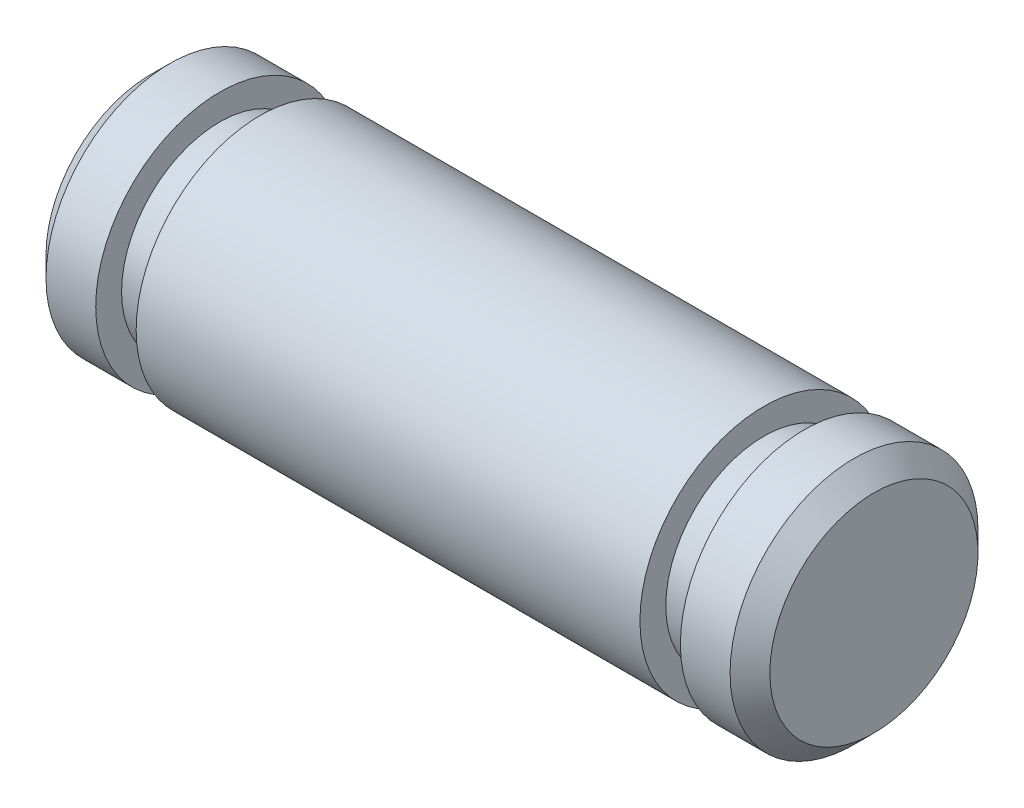
SolidWorks part; units mm, degrees
material "AISI 304"
ref_plane "Front Plane" through (0, 0, 0) normal (0, 0, 1) x (1, 0, 0)
ref_plane "Top Plane" through (0, 0, 0) normal (0, 1, 0) x (1, 0, 0)
ref_plane "Right Plane" through (0, 0, 0) normal (1, 0, 0) x (0, 0, -1)
sketch "Sketch1" plane through (0, 0, 0) normal (0, 0, 1) x (1, 0, 0)
  line L0 (-6.9342, 0) -> (-6.9342, 1.9939)
  line L1 (-6.9342, 1.9939) -> (-6.5532, 2.3749)
  line L2 (-6.5532, 2.3749) -> (-5.6007, 2.3749)
  line L3 (-5.6007, 2.3749) -> (-5.6007, 1.8796)
  line L4 (-5.6007, 1.8796) -> (-4.826, 1.8796)
  line L5 (-4.826, 1.8796) -> (-4.826, 2.3749)
  line L6 (-4.826, 2.3749) -> (4.826, 2.3749)
  line L7 (4.826, 2.3749) -> (4.826, 1.8796)
  line L8 (4.826, 1.8796) -> (5.6007, 1.8796)
  line L9 (5.6007, 1.8796) -> (5.6007, 2.3749)
  line L10 (5.6007, 2.3749) -> (6.5532, 2.3749)
  line L11 (6.5532, 2.3749) -> (6.9342, 1.9939)
  line L12 (6.9342, 1.9939) -> (6.9342, 0)
  line L13 (6.9342, 0) -> (-6.9342, 0)
  line L14 (6.9342, 0) -> (-6.9342, 0) construction
revolve "Revolve1" add sketch "Sketch1" angle 360 about L14 reverse direction yes
ref_plane "Plane1" through (5.2134, 0, 0) normal (1, 0, 0) x (0, 0, -1)
ref_plane "Plane2" through (-5.2134, 0, 0) normal (1, 0, 0) x (0, 0, -1)
ref_plane "p1 XY" through (0, 0, 0) normal (1, 0, 0) x (0, 0, -1)
ref_plane "p1 XZ" through (0, 0, 0) normal (0, -1, 0) x (-1, 0, 0)
ref_plane "p1 YZ" through (0, 0, 2.3749) normal (0, 0, -1) x (-1, 0, 0)
ref_axis "p1 X" through (0, 0, 80.9) along (0, 0, -1)
ref_axis "p1 Y" through (0, -50, 2.3749) along (0, 1, 0)
ref_axis "p1 Z" through (80.9, 0, 2.3749) along (-1, 0, 0)
sketch3d "p1"
  point P0 (0, 0, 2.3749)
ref_plane "p2 XY" through (0, 0, 0) normal (1, 0, 0) x (0, 0, -1)
ref_plane "p2 XZ" through (0, 0, 0) normal (0, -1, 0) x (-1, 0, 0)
ref_plane "p2 YZ" through (0, 0, -2.3749) normal (0, 0, -1) x (-1, 0, 0)
ref_axis "p2 X" through (0, 0, 80.9) along (0, 0, -1)
ref_axis "p2 Y" through (0, -50, -2.3749) along (0, 1, 0)
ref_axis "p2 Z" through (80.9, 0, -2.3749) along (-1, 0, 0)
sketch3d "p2"
  point P0 (0, 0, -2.3749)
ref_plane "pin XY" through (0, 0, 0) normal (1, 0, 0) x (0, 0, -1)
ref_plane "pin XZ" through (0, 0, 0) normal (0, -1, 0) x (-1, 0, 0)
ref_plane "pin YZ" through (0, 0, 0) normal (0, 0, -1) x (-1, 0, 0)
ref_axis "pin X" through (0, 0, 80.9) along (0, 0, -1)
ref_axis "pin Y" through (0, -50, 0) along (0, 1, 0)
ref_axis "pin Z" through (80.9, 0, 0) along (-1, 0, 0)
sketch3d "pin"
  point P0 (0, 0, 0)
ref_plane "rr1 XY" through (5.2134, 0, 0) normal (1, 0, 0) x (0, 0, -1)
ref_plane "rr1 XZ" through (0, 0, 0) normal (0, -1, 0) x (-1, 0, 0)
ref_plane "rr1 YZ" through (0, 0, 0) normal (0, 0, -1) x (-1, 0, 0)
ref_axis "rr1 X" through (5.2134, 0, 80.9) along (0, 0, -1)
ref_axis "rr1 Y" through (5.2134, -50, 0) along (0, 1, 0)
ref_axis "rr1 Z" through (80.9, 0, 0) along (-1, 0, 0)
sketch3d "rr1"
  point P0 (5.2134, 0, 0)
ref_plane "rr2 XY" through (-5.2134, 0, 0) normal (1, 0, 0) x (0, 0, -1)
ref_plane "rr2 XZ" through (0, 0, 0) normal (0, -1, 0) x (-1, 0, 0)
ref_plane "rr2 YZ" through (0, 0, 0) normal (0, 0, -1) x (-1, 0, 0)
ref_axis "rr2 X" through (-5.2134, 0, 80.9) along (0, 0, -1)
ref_axis "rr2 Y" through (-5.2134, -50, 0) along (0, 1, 0)
ref_axis "rr2 Z" through (80.9, 0, 0) along (-1, 0, 0)
sketch3d "rr2"
  point P0 (-5.2134, 0, 0)
ref_plane "w21 XY" through (0, 0, 0) normal (0, 1, 0) x (1, 0, 0)
ref_plane "w21 XZ" through (0, 0, 0) normal (0, 0, 1) x (1, 0, 0)
ref_plane "w21 YZ" through (6.9342, 0, 0) normal (1, 0, 0) x (0, 0, -1)
ref_axis "w21 X" through (-80.9, 0, 0) along (1, 0, 0)
ref_axis "w21 Y" through (6.9342, 0, 50) along (0, 0, -1)
ref_axis "w21 Z" through (6.9342, 50, 0) along (0, -1, 0)
sketch3d "w21"
  point P0 (6.9342, 0, 0)
ref_plane "w22 XY" through (0, 0, 0) normal (0, 1, 0) x (1, 0, 0)
ref_plane "w22 XZ" through (0, 0, 0) normal (0, 0, 1) x (1, 0, 0)
ref_plane "w22 YZ" through (-6.9342, 0, 0) normal (1, 0, 0) x (0, 0, -1)
ref_axis "w22 X" through (-80.9, 0, 0) along (1, 0, 0)
ref_axis "w22 Y" through (-6.9342, 0, 50) along (0, 0, -1)
ref_axis "w22 Z" through (-6.9342, 50, 0) along (0, -1, 0)
sketch3d "w22"
  point P0 (-6.9342, 0, 0)
